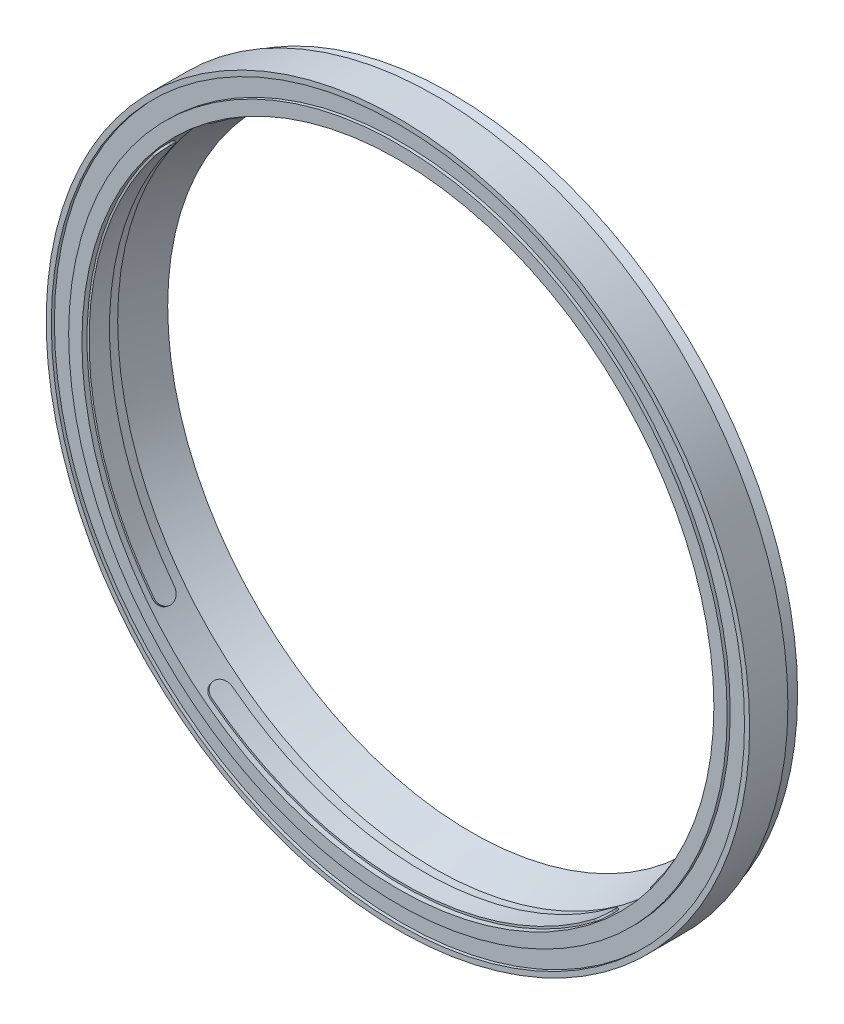
SolidWorks part; units mm, degrees
material "TPU-95A"
ref_plane "Front Plane" through (0, 0, 0) normal (0, 0, 1) x (1, 0, 0)
ref_plane "Top Plane" through (0, 0, 0) normal (0, 1, 0) x (1, 0, 0)
ref_plane "Right Plane" through (0, 0, 0) normal (1, 0, 0) x (0, 0, -1)
sketch "Sketch1" plane through (0, 0, 0) normal (1, 0, 0) x (0, 0, -1)
  line L0 (0, 0) -> (57.7495, 0) construction
  line L1 (3.75, 34.45) -> (3.75, 33.95)
  line L2 (0, 34.45) -> (3.75, 34.45)
  line L3 (3.75, 33.95) -> (5.2, 33.95) construction
  line L4 (5.2, 33.95) -> (3.75, 33.1608)
  line L5 (3.75, 33.1608) -> (3.75, 33.95)
  line L6 (7.2, 30.25) -> (7.2, 29.75)
  line L7 (7.2, 29.75) -> (3.5, 30.95)
  line L8 (3.5, 30.95) -> (0, 30.95)
  line L9 (0, 30.95) -> (0, 32.25)
  line L10 (5.2, 33.95) -> (5.2, 33.0392)
  line L11 (5.2, 33.0392) -> (3.9063, 32.3351)
  line L12 (3.904, 32.1607) -> (7.2, 30.25)
  line L13 (0, 33.95) -> (0.3, 33.95)
  line L14 (0.3, 33.95) -> (0.3, 32.25)
  line L15 (0.3, 32.25) -> (0, 32.25)
  line L16 (0, 33.95) -> (0, 34.45)
  arc A0 (3.9063, 32.3351) -> (3.904, 32.1607) centre (3.9541, 32.2473) ccw
  point P7 (3.75, 32.25)
  dimension "D11" = 64.5
  dimension "D12" = 0.1
  dimension "D1" = 68.9
  dimension "D2" = 3.5
  dimension "D3" = 3.75
  dimension "D4" = 5.2
  dimension "D5" = 0.5
  dimension "D6" = 59.5
  dimension "D7" = 60.5
  dimension "D8" = 0.8
  dimension "D9" = 3.5
  dimension "D10" = 7.2
  dimension "D13" = 0.5
  dimension "D14" = 1.3
  dimension "D15" = 0.3
  dimension "D16" = 61.9
  dimension "D17" = 67.9
  dimension "D18" = 66.0784
  dimension "D19" = 66.3216
revolve "Revolve1" add sketch "Sketch1" angle 360 about L0
ref_plane "Plane1" through (0, 0, -0.5) normal (0, 0, 1) x (1, 0, 0)
sketch "Sketch2" plane through (0, 0, -0.5) normal (0, 0, 1) x (1, 0, 0)
  line L0 (0, 0) -> (0, 24.3515) construction
  line L1 (-19.5022, 23.7745) -> (-21.5, 26.2099)
  line L2 (19.5022, 23.7745) -> (21.5, 26.2099)
  arc A0 (21.5, 26.2099) -> (-21.5, 26.2099) centre (0, 0) ccw
  arc A1 (19.5022, 23.7745) -> (-19.5022, 23.7745) centre (0, 0) ccw
  dimension "D3" = 30.75
  dimension "D1" = 33.9
  dimension "D2" = 43
extrude "Boss-Extrude1" add sketch "Sketch2" against normal blind 2
fillet "Fillet1" radius 1 4 edges at (-19.5656, 23.8518, -2.5) (-19.5656, 23.8518, -0.5) (19.5656, 23.8518, -2.5) (19.5656, 23.8518, -0.5)
pattern_circular "CirPattern1" count 4 over 360 about axis through (0, 0, 0) along (0, 0, 1) of "Boss-Extrude1", "Fillet1"
